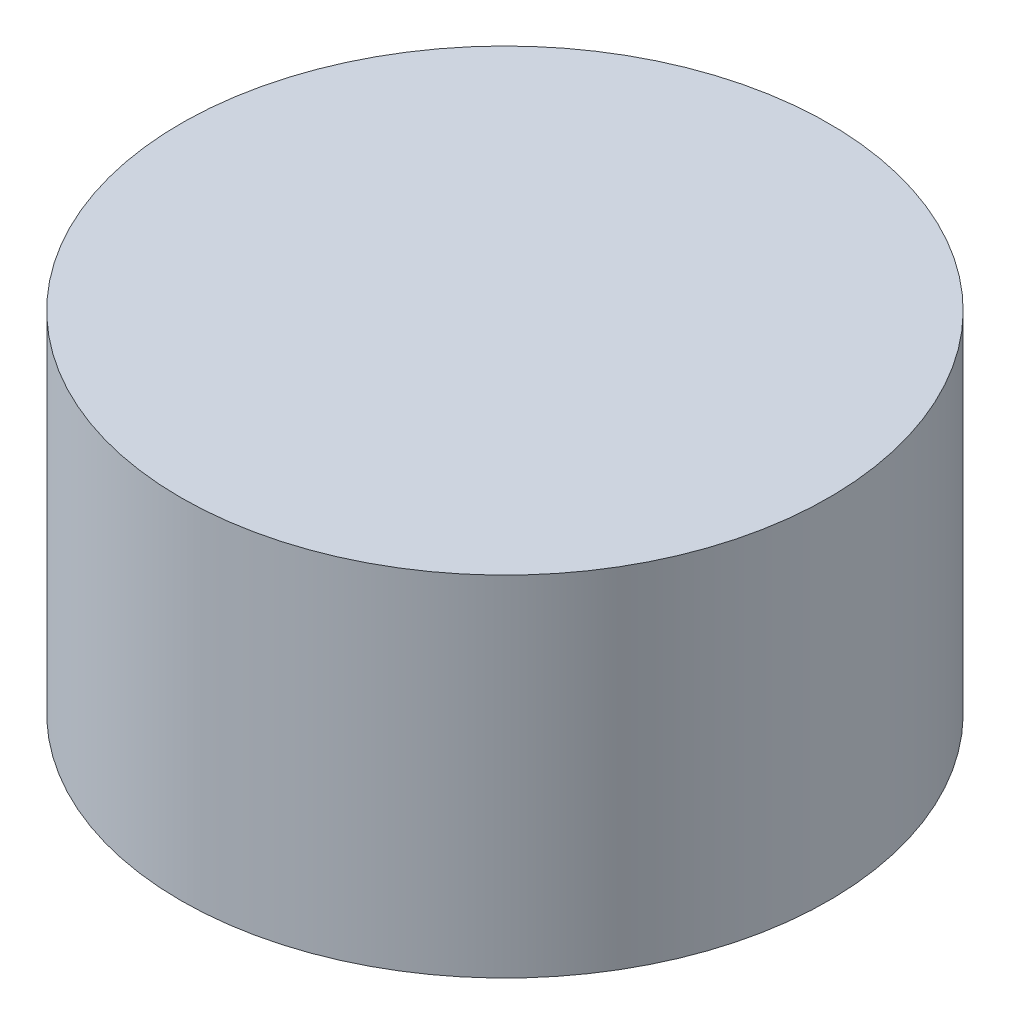
SolidWorks part; units mm, degrees
ref_plane "Front Plane" through (0, 0, 0) normal (0, 0, 1) x (1, 0, 0)
ref_plane "Top Plane" through (0, 0, 0) normal (0, 1, 0) x (1, 0, 0)
ref_plane "Right Plane" through (0, 0, 0) normal (1, 0, 0) x (0, 0, -1)
sketch "Sketch1" plane through (0, 0, 0) normal (0, 1, 0) x (1, 0, 0)
  circle A0 centre (0, 0) radius 13
extrude "Boss-Extrude1" add sketch "Sketch1" along normal blind 14
